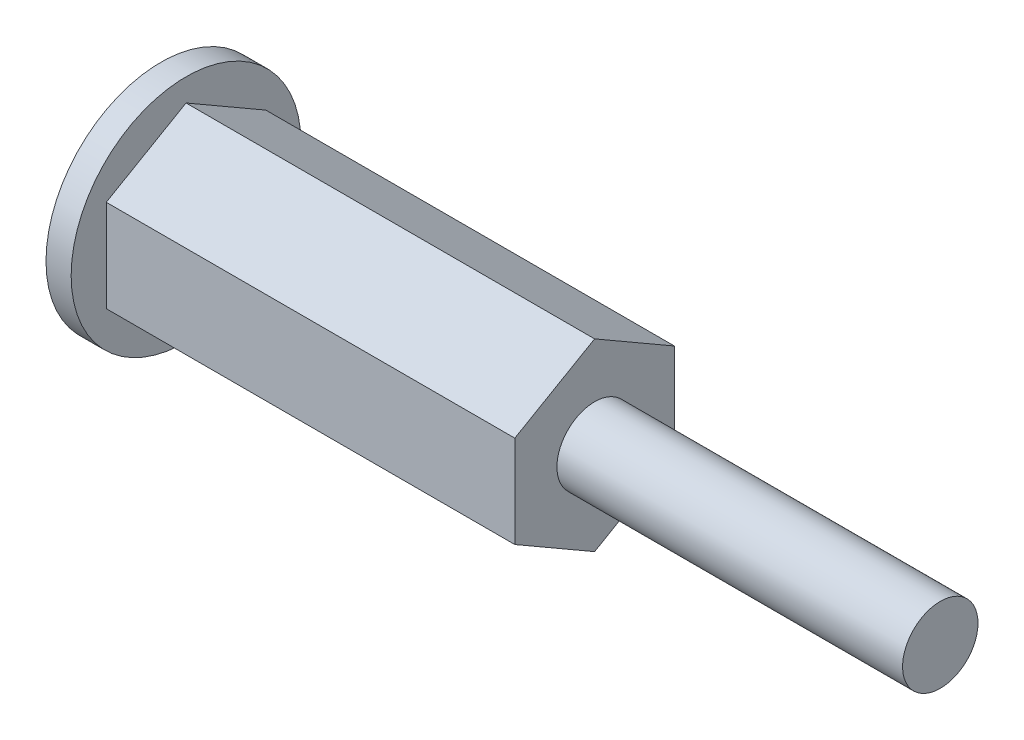
SolidWorks part; units mm, degrees
ref_plane "Front Plane" through (0, 0, 0) normal (1, 0, 0) x (0, 1, 0)
ref_plane "Top Plane" through (0, 0, 0) normal (0, 0, 1) x (0, 1, 0)
ref_plane "Right Plane" through (0, 0, 0) normal (0, 1, 0) x (-1, 0, 0)
sketch "Sketch1" plane through (0, 0, 0) normal (1, 0, 0) x (0, 1, 0)
  circle A0 centre (0, 0) radius 2.999
  dimension "D1" = 5.998
extrude "Boss-Extrude1" add sketch "Sketch1" along normal blind 60
sketch "Sketch2" plane through (0, 0, 0) normal (-1, 0, 0) x (0, -1, 0)
  circle A0 centre (0, 0) radius 9.141
  dimension "D1" = 18.282
extrude "Boss-Extrude2" add sketch "Sketch2" along normal blind 2
sketch "Sketch3" plane through (0, 0, 0) normal (1, 0, 0) x (0, 1, 0)
  line L1 (3.665, 6.348) -> (-3.665, 6.348)
  line L2 (-3.665, 6.348) -> (-7.33, 0)
  line L3 (-7.33, 0) -> (-3.665, -6.348)
  line L4 (-3.665, -6.348) -> (3.665, -6.348)
  line L5 (3.665, -6.348) -> (7.33, 0)
  line L6 (7.33, 0) -> (3.665, 6.348)
  circle A0 centre (0, 0) radius 6.348 construction
  dimension "D2" = 12.6959
  dimension "D1" = 7.33
extrude "Boss-Extrude3" add sketch "Sketch3" along normal blind 32.5
